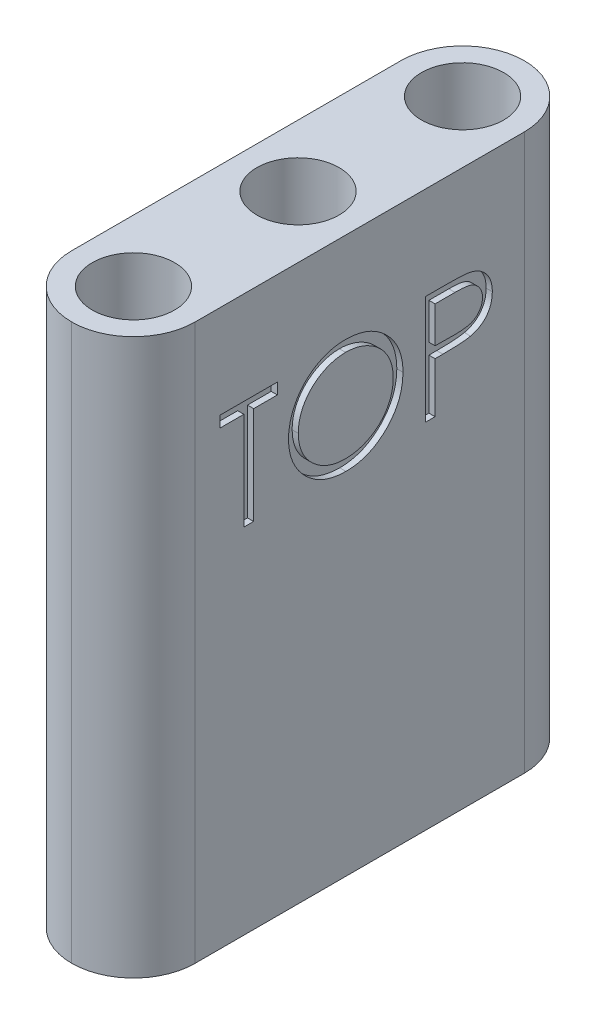
SolidWorks part; units mm, degrees
ref_plane "Front Plane" through (0, 0, 0) normal (0, 0, 1) x (1, 0, 0)
ref_plane "Top Plane" through (0, 0, 0) normal (0, 1, 0) x (1, 0, 0)
ref_plane "Right Plane" through (0, 0, 0) normal (1, 0, 0) x (0, 0, -1)
sketch "Sketch1" plane through (0, 0, 0) normal (0, 1, 0) x (1, 0, 0)
  line L0 (3, -22) -> (3, 0) construction
  line L1 (0, 0) -> (6, 0)
  line L2 (0, 0) -> (0, -22)
  line L3 (0, -22) -> (6, -22)
  line L4 (6, 0) -> (6, -22)
  line L5 (0, -11) -> (6, -11) construction
  circle A0 centre (3, -11) radius 2
  circle A1 centre (3, -19) radius 2
  circle A2 centre (3, -3) radius 2
  dimension "D1" = 4
  dimension "D4" = 4
  dimension "D5" = 3
  dimension "D3" = 3
  dimension "D2" = 8
extrude "Boss-Extrude1" add sketch "Sketch1" along normal blind 27
fillet "Fillet1" radius 3 4 edges at (0, 13.5, 0) (6, 13.5, 0) (0, 13.5, 22) (6, 13.5, 22)
sketch "Sketch2" plane through (6, 0, 0) normal (1, 0, 0) x (0, 0, -1)
  text T0 "\r\nTOP" font "Century Gothic" height in points 20
extrude "Cut-Extrude1" cut sketch "Sketch2" against normal blind 0.3
